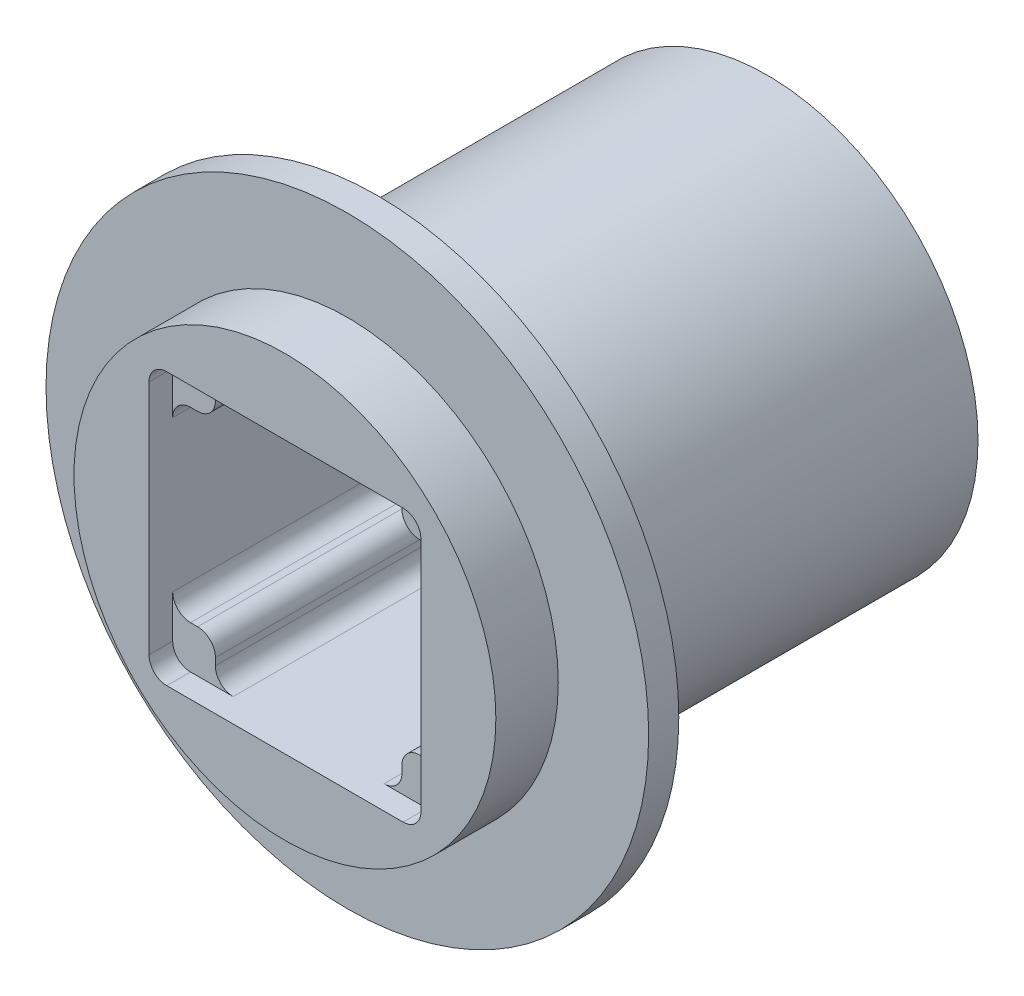
SolidWorks part; units mm, degrees
ref_plane "Front Plane" through (0, 0, 0) normal (0, 0, 1) x (1, 0, 0)
ref_plane "Top Plane" through (0, 0, 0) normal (0, 1, 0) x (1, 0, 0)
ref_plane "Right Plane" through (0, 0, 0) normal (1, 0, 0) x (0, 0, -1)
sketch "Sketch1" plane through (0, 0, 0) normal (0, 0, 1) x (1, 0, 0)
  circle A0 centre (0, 0) radius 44.45
  circle A1 centre (0, 0) radius 63.5
  dimension "D1" = 88.9
  dimension "D2" = 127
extrude "Boss-Extrude1" add sketch "Sketch1" along normal blind 6.35 contours A1 A0 | A0 region at (-61.7039, 0, 0)
extrude "Boss-Extrude2" add sketch "Sketch1<3>" against normal blind 101.6 from offset 19.5 contours A0 region at (0, 0, 0)
sketch "Sketch1<3>" plane through (0, 0, 0) normal (0, 0, 1) x (1, 0, 0) same geometry as "Sketch1"
sketch "Sketch2" plane through (0, 0, 19.5) normal (0, 0, -1) x (-1, 0, 0)
  line L0 (-19.65, 28.65) -> (-19.65, 19.65)
  line L1 (-28.65, -28.65) -> (28.65, -28.65) construction
  line L2 (-28.65, -28.65) -> (-28.65, 28.65) construction
  line L3 (-28.65, 28.65) -> (28.65, 28.65) construction
  line L4 (28.65, -28.65) -> (28.65, 28.65) construction
  line L5 (-28.65, -28.65) -> (28.65, 28.65) construction
  line L6 (-28.65, 28.65) -> (28.65, -28.65) construction
  line L7 (-19.65, 19.65) -> (-28.65, 19.65)
  line L8 (-28.65, 19.65) -> (-28.65, -19.65)
  line L9 (-28.65, -19.65) -> (-19.65, -19.65)
  line L10 (-19.65, -19.65) -> (-19.65, -28.65)
  line L11 (-19.65, -28.65) -> (19.65, -28.65)
  line L12 (19.65, -28.65) -> (19.65, -19.65)
  line L13 (19.65, -19.65) -> (28.65, -19.65)
  line L14 (28.65, -19.65) -> (28.65, 19.65)
  line L15 (28.65, 19.65) -> (19.65, 19.65)
  line L16 (19.65, 19.65) -> (19.65, 28.65)
  line L17 (19.65, 28.65) -> (-19.65, 28.65)
  point P0 (0, 0)
  dimension "D1" = 57.3
  dimension "D2" = 9
extrude "Cut-Extrude1" cut sketch "Sketch2" along normal through all
fillet "Fillet1" radius 3.75 12 edges at (19.65, -19.65, -31.3) (-19.65, -19.65, -31.3) (-19.65, 19.65, -31.3) (19.65, 19.65, -31.3) (-28.65, 19.65, -31.3) (-19.65, -28.65, -31.3) (19.65, -28.65, -31.3) (28.65, -19.65, -31.3) (28.65, 19.65, -31.3) (19.65, 28.65, -31.3) (-19.65, 28.65, -31.3) (-28.65, -19.65, -31.3)
sketch "Sketch3" plane through (0, 0, 19.5) normal (0, 0, -1) x (-1, 0, 0)
  line L1 (-24.9, -28.65) -> (24.9, -28.65)
  line L2 (-28.65, -24.9) -> (-28.65, 24.9)
  line L3 (-24.9, 28.65) -> (24.9, 28.65)
  line L4 (28.65, -24.9) -> (28.65, 24.9)
  line L5 (-28.65, -28.65) -> (28.65, 28.65) construction
  line L6 (-28.65, 28.65) -> (28.65, -28.65) construction
  arc A0 (-24.9, -28.65) -> (-28.65, -24.9) centre (-24.9, -24.9) cw
  arc A1 (24.9, -28.65) -> (28.65, -24.9) centre (24.9, -24.9) ccw
  arc A2 (24.9, 28.65) -> (28.65, 24.9) centre (24.9, 24.9) cw
  arc A3 (-28.65, 24.9) -> (-24.9, 28.65) centre (-24.9, 24.9) cw
  point P0 (0, 0)
  dimension "D2" = 3.75
  dimension "D1" = 57.3
extrude "Cut-Extrude2" cut sketch "Sketch3" along normal blind 5
